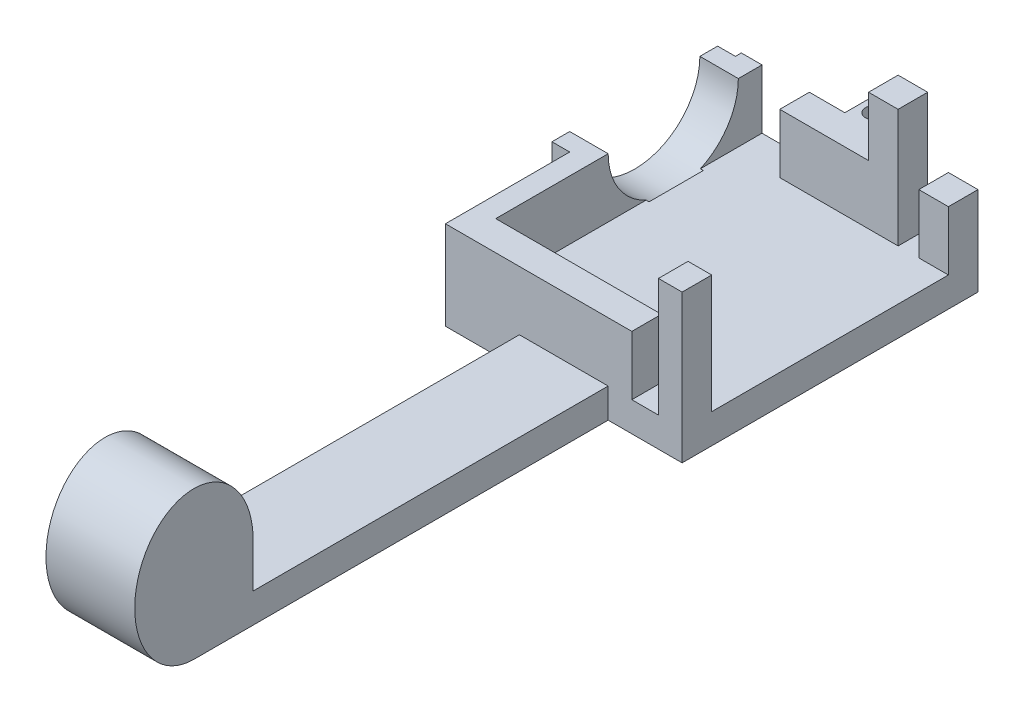
SolidWorks part; units mm, degrees
note: The reader was unsure of these and kept them because the rebuilt part matched: shared geometry of "Sketch3<3>".
ref_plane "Front Plane" through (0, 0, 0) normal (0, 0, 1) x (1, 0, 0)
ref_plane "Top Plane" through (0, 0, 0) normal (0, 1, 0) x (1, 0, 0)
ref_plane "Right Plane" through (0, 0, 0) normal (1, 0, 0) x (0, 0, -1)
sketch "Sketch1" plane through (0, 0, 0) normal (0, 1, 0) x (1, 0, 0)
  line L1 (-20, 25) -> (20, 25)
  line L2 (-20, 25) -> (-20, -25)
  line L3 (-20, -25) -> (20, -25)
  line L4 (20, 25) -> (20, -25)
  point P6 (20, 0)
  point P7 (0, 25)
  dimension "D1" = 40
  dimension "D2" = 50
extrude "Boss-Extrude1" add sketch "Sketch1" along normal blind 5
sketch "Sketch3" plane through (0, 5, 0) normal (0, 1, 0) x (1, 0, 0)
  line L0 (20, 25) -> (-20, 25) construction
  line L1 (-8.5, 25) -> (6.5, 25)
  line L2 (-8.5, 25) -> (-8.5, 20)
  line L3 (-8.5, 20) -> (6.5, 20)
  line L4 (6.5, 25) -> (6.5, 20)
  line L6 (-20, -25) -> (20, -25) construction
  line L7 (-20, 25) -> (-16.5, 25)
  line L10 (-16.5, 25) -> (-16.5, -20)
  line L11 (20, -25) -> (16, -25)
  line L12 (20, -25) -> (20, -20)
  line L13 (20, -20) -> (16, -20)
  line L14 (16, -25) -> (16, -20)
  line L15 (6.5, -25) -> (-20, -25)
  line L16 (6.5, -25) -> (6.5, -20)
  line L17 (6.5, -20) -> (-16.5, -20)
  line L20 (20, 25) -> (15, 25)
  line L21 (20, 25) -> (20, 20)
  line L22 (-20, 25) -> (-20, -25)
  line L23 (6.5, -20) -> (11.5, -20)
  line L24 (6.5, -20) -> (6.5, -25)
  line L25 (20, 20) -> (15, 20)
  line L26 (6.5, 20) -> (11.5, 20)
  line L27 (6.5, 20) -> (6.5, 25)
  line L28 (6.5, 25) -> (11.5, 25)
  line L29 (11.5, 20) -> (11.5, 25)
  line L30 (15, 25) -> (15, 20)
  line L31 (6.5, -25) -> (11.5, -25)
  line L32 (11.5, -20) -> (11.5, -25)
  line M17 (-20, 25) -> (-20, -25)
  line M18 (-20, -25) -> (20, -25)
  line M19 (20, -25) -> (20, 25)
  line M20 (20, 25) -> (-20, 25)
  dimension "D1" = 8
  dimension "D2" = 15
  dimension "D3" = 3.5
  dimension "D4" = 5
  dimension "D5" = 4
  dimension "D7" = 5
extrude "Boss-Extrude5" add sketch "Sketch3" along normal blind 20 contours L14 L13 M18 M19 | L26 L29 L4 M20
extrude "Boss-Extrude6" add sketch "Sketch3<3>" along normal blind 10 contours L4 L2 L3 M20 | L16 L17 L10 M20 M17 M18 | L21 L20 L30 L25 | L24 L23 L32 L31
sketch "Sketch3<3>" plane through (0, 5, 0) normal (0, 1, 0) x (1, 0, 0) same geometry as "Sketch3"
sketch "Sketch8" plane through (-20, 0, 0) normal (-1, 0, 0) x (0, 0, 1)
  line L0 (-25, 15) -> (25, 15) construction
  line L1 (1, 15) -> (-21, 15)
  arc A0 (-21, 15) -> (1, 15) centre (-10, 15) ccw
  dimension "D1" = 22
  dimension "D2" = 4
extrude "Cut-Extrude3" cut sketch "Sketch8" against normal blind 4
sketch "Sketch10" plane through (-20, 0, 0) normal (-1, 0, 0) x (0, 0, 1)
  line L0 (1, 15) -> (4, 15)
  line L1 (1, 15) -> (25, 15) construction
  line L2 (4, 15) -> (4, 0)
  line L3 (-25, 0) -> (25, 0) construction
  line L4 (4, 0) -> (-24, 0)
  line L5 (-24, 0) -> (-24, 15)
  line L6 (-25, 15) -> (-21, 15) construction
  line L7 (-24, 15) -> (-21, 15)
  arc A0 (-21, 15) -> (1, 15) centre (-10, 15) ccw
  dimension "D2" = 11
  dimension "D1" = 3
extrude "Boss-Extrude9" add sketch "Sketch10" along normal blind 3
sketch "Sketch12" plane through (0, 0, -25) normal (0, 0, -1) x (-1, 0, 0)
  line L0 (-6.5, 15) -> (8.5, 15) construction
  line L1 (-2.5, 15) -> (2.5, 15)
  line L2 (-2.5, 15) -> (-2.5, 10)
  line L3 (-2.5, 10) -> (2.5, 10)
  line L4 (2.5, 15) -> (2.5, 10)
  point P6 (0, 10)
  dimension "D1" = 5
  dimension "D2" = 5
extrude "Boss-Extrude10" add sketch "Sketch12" along normal blind 5
sketch "Sketch13" plane through (0, 10, 0) normal (0, -1, 0) x (1, 0, 0)
  line L0 (20, -25) -> (-20, -25) construction
  line L1 (-2.5, -30) -> (-2.5, -25) construction
  circle A0 centre (0, -27.5) radius 1.5
  point P4 (0, -25)
  point P7 (-2.5, -27.5)
  dimension "D1" = 3
extrude "Cut-Extrude4" cut sketch "Sketch13" against normal blind 5
sketch "Sketch14" plane through (0, 0, 25) normal (0, 0, 1) x (1, 0, 0)
  line L0 (-20, 0) -> (20, 0) construction
  line L1 (7.5, 0) -> (-7.5, 0)
  line L2 (7.5, 0) -> (7.5, 5)
  line L3 (7.5, 5) -> (-7.5, 5)
  line L4 (-7.5, 0) -> (-7.5, 5)
  point P6 (0, 5)
  dimension "D1" = 5
  dimension "D2" = 15
extrude "Boss-Extrude11" add sketch "Sketch14" along normal blind 80
sketch "Sketch15" plane through (0, 5, 0) normal (0, 1, 0) x (1, 0, 0)
  line L0 (7.5, -105) -> (7.5, -25) construction
  line L1 (-7.5, -105) -> (7.5, -105)
  line L2 (-7.5, -105) -> (-7.5, -85)
  line L3 (-7.5, -85) -> (7.5, -85)
  line L4 (7.5, -105) -> (7.5, -85)
  dimension "D1" = 20
extrude "Boss-Extrude13" add sketch "Sketch15" along normal blind 20
sketch "Sketch16" plane through (-7.5, 0, 0) normal (-1, 0, 0) x (0, 0, 1)
  line L1 (95, 12.5) -> (95, 25) construction
  line L2 (85, 12.5) -> (85, 25)
  line L3 (105, 12.5) -> (85, 12.5) construction
  line L4 (105, 25) -> (105, 0) construction
  line L5 (85, 25) -> (85, 5) construction
  line L6 (85, 25) -> (95, 25)
  line L7 (95, 25) -> (105, 25)
  line L8 (85, 25) -> (105, 25) construction
  line L9 (105, 0) -> (25, 0) construction
  line L10 (105, 25) -> (105, 0)
  line L11 (105, 0) -> (95, 0)
  ellipse E0 centre (95, 12.5) end of major axis (95, 25) minor radius 10 (95, 0) -> (85, 12.5) ccw
  point P15 (0, 0)
  point P23 (0, 0)
extrude "Cut-Extrude5" cut sketch "Sketch16" against normal blind 15 contours E0 L3 L4 | E0 L10 L3 | E0 L2
